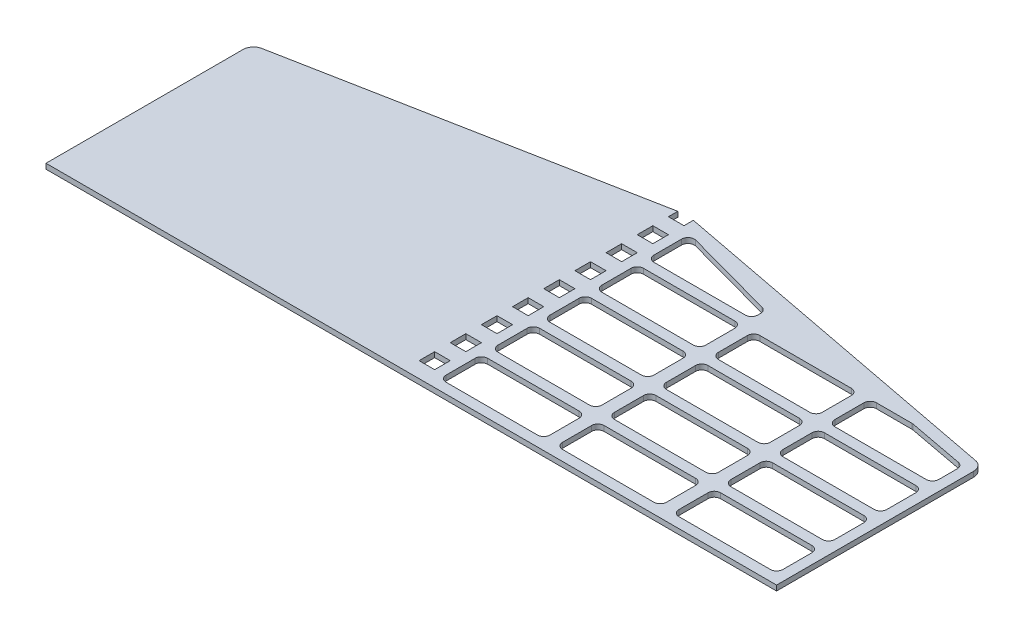
SolidWorks part; units mm, degrees
material "Balsa"
ref_plane "Front Plane" through (0, 0, 0) normal (0, 0, 1) x (1, 0, 0)
ref_plane "Top Plane" through (0, 0, 0) normal (0, 1, 0) x (1, 0, 0)
ref_plane "Right Plane" through (0, 0, 0) normal (1, 0, 0) x (0, 0, -1)
sketch "Sketch1" plane through (0, 0, 0) normal (0, 1, 0) x (1, 0, 0)
  line L0 (0, 0) -> (437.0222, 0)
  line L1 (426.7145, 253.437) -> (0, 335.28)
  line L2 (0, 335.28) -> (0, 0)
  line L3 (437.0222, 0) -> (437.0222, 240.9644)
  arc A0 (426.7145, 253.437) -> (437.0222, 240.9644) centre (424.3222, 240.9644) cw
  point P7 (437.0222, 251.46)
  dimension "D4" = 12.7
  dimension "D1" = 335.28
  dimension "D2" = 437.0222
  dimension "D3" = 251.46
extrude "Boss-Extrude1" add sketch "Sketch1" along normal blind 6.35
sketch "Sketch2" plane through (0, 6.35, 0) normal (0, 1, 0) x (1, 0, 0)
  line L0 (0, 0) -> (437.0222, 0) construction
  line L1 (20.32, 12.7) -> (132.08, 12.7)
  line L2 (12.7, 20.32) -> (12.7, 55.88)
  line L3 (20.32, 63.5) -> (132.08, 63.5)
  line L4 (139.7, 20.32) -> (139.7, 55.88)
  line L9 (0, 335.28) -> (0, 0) construction
  line L10 (155.045, 20.32) -> (155.045, 55.88)
  line L11 (162.665, 12.7) -> (274.425, 12.7)
  line L12 (282.045, 20.32) -> (282.045, 55.88)
  line L13 (162.665, 63.5) -> (274.425, 63.5)
  line L14 (297.3901, 20.32) -> (297.3901, 55.88)
  line L15 (305.0101, 12.7) -> (416.7701, 12.7)
  line L16 (424.3901, 20.32) -> (424.3901, 55.88)
  line L17 (305.0101, 63.5) -> (416.7701, 63.5)
  line L18 (155.045, 83.82) -> (155.045, 119.38)
  line L19 (162.665, 76.2) -> (274.425, 76.2)
  line L20 (282.045, 83.82) -> (282.045, 119.38)
  line L21 (162.665, 127) -> (274.425, 127)
  line L22 (297.3901, 83.82) -> (297.3901, 119.38)
  line L23 (305.0101, 76.2) -> (416.7701, 76.2)
  line L24 (424.3901, 83.82) -> (424.3901, 119.38)
  line L25 (305.0101, 127) -> (416.7701, 127)
  line L26 (155.045, 147.32) -> (155.045, 182.88)
  line L27 (162.665, 139.7) -> (274.425, 139.7)
  line L28 (282.045, 147.32) -> (282.045, 182.88)
  line L29 (162.665, 190.5) -> (274.425, 190.5)
  line L30 (297.3901, 147.32) -> (297.3901, 182.88)
  line L31 (305.0101, 139.7) -> (416.7701, 139.7)
  line L32 (424.3901, 147.32) -> (424.3901, 182.88)
  line L33 (305.0101, 190.5) -> (416.7701, 190.5)
  line L34 (155.045, 210.82) -> (155.045, 246.38)
  line L35 (162.665, 203.2) -> (274.425, 203.2)
  line L36 (282.045, 210.82) -> (282.045, 246.38)
  line L37 (162.665, 254) -> (274.425, 254)
  line L38 (297.3901, 210.82) -> (297.3901, 246.38)
  line L39 (305.0101, 203.2) -> (416.7701, 203.2)
  line L40 (424.3901, 210.82) -> (424.3901, 233.5456)
  line L41 (305.0101, 254) -> (348.5374, 254)
  line L50 (12.7, 83.82) -> (12.7, 119.38)
  line L51 (20.32, 76.2) -> (132.08, 76.2)
  line L52 (139.7, 83.82) -> (139.7, 119.38)
  line L53 (20.32, 127) -> (132.08, 127)
  line L54 (12.7, 147.32) -> (12.7, 182.88)
  line L55 (20.32, 139.7) -> (132.08, 139.7)
  line L56 (139.7, 147.32) -> (139.7, 182.88)
  line L57 (20.32, 190.5) -> (132.08, 190.5)
  line L58 (12.7, 210.8976) -> (12.7, 246.3024)
  line L59 (20.3976, 203.2) -> (132.0024, 203.2)
  line L60 (139.7, 210.8976) -> (139.7, 246.3024)
  line L61 (20.3976, 254) -> (132.0024, 254)
  line L62 (12.7, 274.3976) -> (12.7, 308.3078)
  line L63 (20.3976, 266.7) -> (132.0024, 266.7)
  line L64 (139.7, 274.3976) -> (139.7, 277.7658)
  line L66 (22.4294, 315.7324) -> (134.0343, 285.1904)
  line L68 (12.7, 317.5) -> (106.9847, 317.5) [skipped]
  line L69 (154.94, 317.5) -> (281.94, 317.5) [skipped]
  line L70 (282.045, 364.4738) -> (282.045, 415.2738) [skipped]
  line L71 (297.3901, 266.7) -> (297.3901, 317.5) [skipped]
  line L72 (297.18, 317.5) -> (424.18, 317.5) [skipped]
  line L73 (424.3901, 266.7) -> (424.3901, 317.5) [skipped]
  line L74 (297.18, 266.7) -> (424.18, 266.7) [skipped]
  line L75 (349.946, 253.8687) -> (418.1787, 241.0342)
  line L77 (162.665, 266.7) -> (200.4554, 266.7) [skipped]
  line L78 (155.045, 286.9363) -> (155.045, 297.2637) [skipped]
  arc A0 (20.32, 12.7) -> (12.7, 20.32) centre (20.32, 20.32) cw
  arc A1 (12.7, 55.88) -> (20.32, 63.5) centre (20.32, 55.88) cw
  arc A2 (132.08, 63.5) -> (139.7, 55.88) centre (132.08, 55.88) cw
  arc A3 (132.08, 12.7) -> (139.7, 20.32) centre (132.08, 20.32) ccw
  arc A4 (155.045, 20.32) -> (162.665, 12.7) centre (162.665, 20.32) ccw
  arc A5 (155.045, 55.88) -> (162.665, 63.5) centre (162.665, 55.88) cw
  arc A6 (282.045, 55.88) -> (274.425, 63.5) centre (274.425, 55.88) ccw
  arc A7 (274.425, 12.7) -> (282.045, 20.32) centre (274.425, 20.32) ccw
  arc A8 (416.7701, 12.7) -> (424.3901, 20.32) centre (416.7701, 20.32) ccw
  arc A9 (297.3901, 20.32) -> (305.0101, 12.7) centre (305.0101, 20.32) ccw
  arc A10 (297.3901, 55.88) -> (305.0101, 63.5) centre (305.0101, 55.88) cw
  arc A11 (424.3901, 55.88) -> (416.7701, 63.5) centre (416.7701, 55.88) ccw
  arc A12 (424.3901, 119.38) -> (416.7701, 127) centre (416.7701, 119.38) ccw
  arc A13 (416.7701, 76.2) -> (424.3901, 83.82) centre (416.7701, 83.82) ccw
  arc A14 (297.3901, 83.82) -> (305.0101, 76.2) centre (305.0101, 83.82) ccw
  arc A15 (297.3901, 119.38) -> (305.0101, 127) centre (305.0101, 119.38) cw
  arc A16 (282.045, 119.38) -> (274.425, 127) centre (274.425, 119.38) ccw
  arc A17 (282.045, 83.82) -> (274.425, 76.2) centre (274.425, 83.82) cw
  arc A18 (155.045, 83.82) -> (162.665, 76.2) centre (162.665, 83.82) ccw
  arc A19 (155.045, 119.38) -> (162.665, 127) centre (162.665, 119.38) cw
  arc A20 (139.7, 119.38) -> (132.08, 127) centre (132.08, 119.38) ccw
  arc A21 (132.08, 76.2) -> (139.7, 83.82) centre (132.08, 83.82) ccw
  arc A22 (12.7, 83.82) -> (20.32, 76.2) centre (20.32, 83.82) ccw
  arc A23 (12.7, 119.38) -> (20.32, 127) centre (20.32, 119.38) cw
  arc A24 (12.7, 147.32) -> (20.32, 139.7) centre (20.32, 147.32) ccw
  arc A25 (12.7, 182.88) -> (20.32, 190.5) centre (20.32, 182.88) cw
  arc A26 (139.7, 182.88) -> (132.08, 190.5) centre (132.08, 182.88) ccw
  arc A27 (132.08, 139.7) -> (139.7, 147.32) centre (132.08, 147.32) ccw
  arc A28 (155.045, 147.32) -> (162.665, 139.7) centre (162.665, 147.32) ccw
  arc A29 (155.045, 182.88) -> (162.665, 190.5) centre (162.665, 182.88) cw
  arc A30 (274.425, 139.7) -> (282.045, 147.32) centre (274.425, 147.32) ccw
  arc A31 (282.045, 182.88) -> (274.425, 190.5) centre (274.425, 182.88) ccw
  arc A32 (297.3901, 182.88) -> (305.0101, 190.5) centre (305.0101, 182.88) cw
  arc A33 (297.3901, 147.32) -> (305.0101, 139.7) centre (305.0101, 147.32) ccw
  arc A34 (416.7701, 139.7) -> (424.3901, 147.32) centre (416.7701, 147.32) ccw
  arc A35 (424.3901, 182.88) -> (416.7701, 190.5) centre (416.7701, 182.88) ccw
  arc A36 (418.1787, 241.0342) -> (424.3901, 233.5456) centre (416.7701, 233.5456) cw
  arc A37 (348.5374, 254) -> (349.946, 253.8687) centre (348.5374, 246.38) cw
  arc A38 (297.3901, 210.82) -> (305.0101, 203.2) centre (305.0101, 210.82) ccw
  arc A39 (416.7701, 203.2) -> (424.3901, 210.82) centre (416.7701, 210.82) ccw
  arc A40 (297.3901, 246.38) -> (305.0101, 254) centre (305.0101, 246.38) cw
  arc A41 (155.045, 246.38) -> (162.665, 254) centre (162.665, 246.38) cw
  arc A42 (155.045, 210.82) -> (162.665, 203.2) centre (162.665, 210.82) ccw
  arc A44 (274.425, 203.2) -> (282.045, 210.82) centre (274.425, 210.82) ccw
  arc A45 (282.045, 246.38) -> (274.425, 254) centre (274.425, 246.38) ccw
  arc A48 (139.7, 246.3024) -> (132.0024, 254) centre (132.0024, 246.3024) ccw
  arc A49 (132.0024, 203.2) -> (139.7, 210.8976) centre (132.0024, 210.8976) ccw
  arc A50 (12.7, 210.8976) -> (20.3976, 203.2) centre (20.3976, 210.8976) ccw
  arc A51 (12.7, 246.3024) -> (20.3976, 254) centre (20.3976, 246.3024) cw
  arc A52 (12.7, 274.3976) -> (20.3976, 266.7) centre (20.3976, 274.3976) ccw
  arc A53 (132.0024, 266.7) -> (139.7, 274.3976) centre (132.0024, 274.3976) ccw
  arc A54 (139.7, 277.7658) -> (134.0343, 285.1904) centre (132.0024, 277.7658) ccw
  arc A55 (12.7, 308.3078) -> (22.4294, 315.7324) centre (20.3976, 308.3078) cw
  point P46 (12.7, 12.7)
  point P49 (12.7, 63.5)
  point P82 (139.7, 63.5)
  dimension "D7" = 7.62
  dimension "D1" = 127
  dimension "D2" = 50.8
  dimension "D3" = 12.7
  dimension "D4" = 12.7
  dimension "D5" = 3
  dimension "D6" = 5
extrude "Cut-Extrude1" cut sketch "Sketch2" against normal up to surface (6.35 mm away) up to face at (260.6005, 0, -166.3071)
sketch "Sketch3" plane through (0, 6.35, 0) normal (0, 1, 0) x (1, 0, 0)
  line L2 (0, 19.05) -> (0, 38.1)
  line L3 (0, 0) -> (-19.05, 0)
  line L4 (0, 0) -> (0, 19.05)
  line L5 (0, 19.05) -> (-19.05, 19.05)
  line L6 (-19.05, 0) -> (-19.05, 19.05)
  line L7 (0, 19.05) -> (-19.05, 19.05)
  line L8 (-19.05, 19.05) -> (-19.05, 38.1)
  line L9 (0, 38.1) -> (-19.05, 38.1)
  line L10 (0, 38.1) -> (0, 57.15)
  line L11 (0, 38.1) -> (-19.05, 38.1)
  line L12 (-19.05, 38.1) -> (-19.05, 57.15)
  line L13 (0, 57.15) -> (-19.05, 57.15)
  line L14 (0, 57.15) -> (0, 76.2)
  line L15 (0, 57.15) -> (-19.05, 57.15)
  line L16 (-19.05, 57.15) -> (-19.05, 76.2)
  line L17 (0, 76.2) -> (-19.05, 76.2)
  line L18 (0, 76.2) -> (0, 95.25)
  line L19 (0, 76.2) -> (-19.05, 76.2)
  line L20 (-19.05, 76.2) -> (-19.05, 95.25)
  line L21 (0, 95.25) -> (-19.05, 95.25)
  line L22 (0, 95.25) -> (0, 114.3)
  line L23 (0, 95.25) -> (-19.05, 95.25)
  line L24 (-19.05, 95.25) -> (-19.05, 114.3)
  line L25 (0, 114.3) -> (-19.05, 114.3)
  line L26 (0, 114.3) -> (0, 133.35)
  line L27 (0, 114.3) -> (-19.05, 114.3)
  line L28 (-19.05, 114.3) -> (-19.05, 133.35)
  line L29 (0, 133.35) -> (-19.05, 133.35)
  line L30 (0, 133.35) -> (0, 152.4)
  line L31 (0, 133.35) -> (-19.05, 133.35)
  line L32 (-19.05, 133.35) -> (-19.05, 152.4)
  line L33 (0, 152.4) -> (-19.05, 152.4)
  line L34 (0, 152.4) -> (0, 171.45)
  line L35 (0, 152.4) -> (-19.05, 152.4)
  line L36 (-19.05, 152.4) -> (-19.05, 171.45)
  line L37 (0, 171.45) -> (-19.05, 171.45)
  line L38 (0, 171.45) -> (0, 190.5)
  line L39 (0, 171.45) -> (-19.05, 171.45)
  line L40 (-19.05, 171.45) -> (-19.05, 190.5)
  line L41 (0, 190.5) -> (-19.05, 190.5)
  line L42 (0, 190.5) -> (0, 209.55)
  line L43 (0, 190.5) -> (-19.05, 190.5)
  line L44 (-19.05, 190.5) -> (-19.05, 209.55)
  line L45 (0, 209.55) -> (-19.05, 209.55)
  line L46 (0, 209.55) -> (0, 228.6)
  line L47 (0, 209.55) -> (-19.05, 209.55)
  line L48 (-19.05, 209.55) -> (-19.05, 228.6)
  line L49 (0, 228.6) -> (-19.05, 228.6)
  line L50 (0, 228.6) -> (0, 247.65)
  line L51 (0, 228.6) -> (-19.05, 228.6)
  line L52 (-19.05, 228.6) -> (-19.05, 247.65)
  line L53 (0, 247.65) -> (-19.05, 247.65)
  line L54 (0, 247.65) -> (0, 266.7)
  line L55 (0, 247.65) -> (-19.05, 247.65)
  line L56 (-19.05, 247.65) -> (-19.05, 266.7)
  line L57 (0, 266.7) -> (-19.05, 266.7)
  line L58 (0, 266.7) -> (0, 285.75)
  line L59 (0, 266.7) -> (-19.05, 266.7)
  line L60 (-19.05, 266.7) -> (-19.05, 285.75)
  line L61 (0, 285.75) -> (-19.05, 285.75)
  line L62 (0, 285.75) -> (0, 304.8)
  line L63 (0, 285.75) -> (-19.05, 285.75)
  line L64 (-19.05, 285.75) -> (-19.05, 304.8)
  line L65 (0, 304.8) -> (-19.05, 304.8)
  line L66 (0, 304.8) -> (0, 323.85)
  line L67 (0, 304.8) -> (-19.05, 304.8)
  line L68 (-19.05, 304.8) -> (-19.05, 323.85)
  line L69 (0, 323.85) -> (-19.05, 323.85)
  line L70 (0, 323.85) -> (0, 342.9)
  line L71 (0, 323.85) -> (-19.05, 323.85)
  line L72 (-19.05, 323.85) -> (-19.05, 342.9)
  line L73 (0, 342.9) -> (-19.05, 342.9)
  dimension "D2" = 19.05
  dimension "D3" = 19.05
  dimension "D4" = 18
extrude "Boss-Extrude2" add sketch "Sketch3" against normal up to surface (6.35 mm away) contours L6 L3 L4 L5 | L10 L13 L12 L9 | L18 L21 L20 L17 | L26 L29 L28 L25 | L34 L37 L36 L33 | L42 L45 L44 L41 | L50 L53 L52 L49 | L58 L61 L60 L57 | L66 L69 L68 L65 region at (-9.525, 6.35, -9.525) region at (-9.525, 6.35, -47.625) region at (-9.525, 6.35, -85.725) region at (-9.525, 6.35, -123.825) region at (-9.525, 6.35, -161.925) region at (-9.525, 6.35, -200.025) region at (-9.525, 6.35, -238.125) region at (-9.525, 6.35, -276.225) region at (-9.525, 6.35, -314.325) up to face at (76.6352, 0, -283.6709)
ref_plane "Plane1" through (-9.525, 0, 0) normal (-1, 0, 0) x (0, 0, 1)
mirror "Mirror1" about plane through (-9.525, 0, 0) normal (-1, 0, 0) of "Boss-Extrude1"
